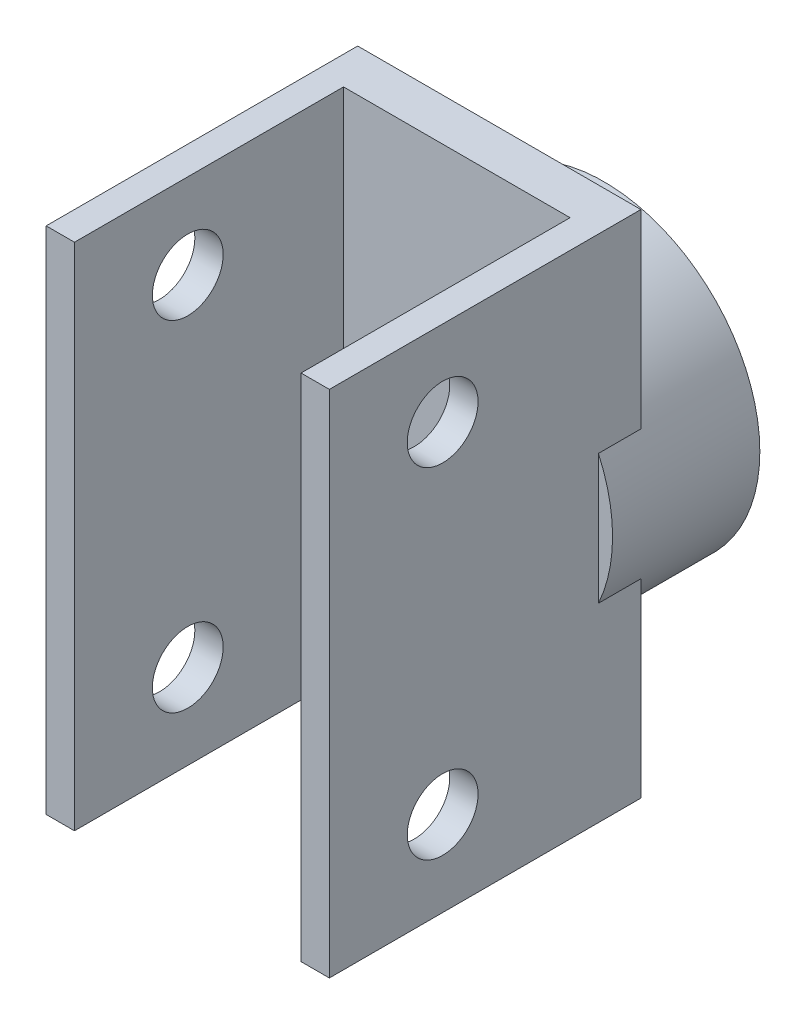
SolidWorks part; units mm, degrees
ref_plane "Front Plane" through (0, 0, 0) normal (0, 0, 1) x (1, 0, 0)
ref_plane "Top Plane" through (0, 0, 0) normal (0, 1, 0) x (1, 0, 0)
ref_plane "Right Plane" through (0, 0, 0) normal (1, 0, 0) x (0, 0, -1)
sketch "Sketch1" plane through (0, 0, 0) normal (0, 0, 1) x (1, 0, 0)
  circle A14 centre (30.5, 45) radius 11
  arc A28 (39.3036, 49.7431) -> (38.5512, 50.9312) centre (30.5, 45) ccw
  arc A29 (33.7877, 49.8991) -> (33.4512, 50.1088) centre (30.5, 45) ccw
  arc A30 (32.2807, 54.8402) -> (30.8827, 54.9927) centre (30.5, 45) ccw
  arc A31 (28.7196, 50.625) -> (28.3458, 50.4927) centre (30.5, 45) ccw
  arc A32 (23.9169, 52.5274) -> (22.926, 51.5295) centre (30.5, 45) ccw
  arc A33 (24.9922, 47.1151) -> (24.8625, 46.7404) centre (30.5, 45) ccw
  arc A34 (20.5103, 44.5464) -> (20.6727, 43.1495) centre (30.5, 45) ccw
  arc A35 (25.4123, 42.0126) -> (25.6244, 41.6776) centre (30.5, 45) ccw
  arc A36 (24.6262, 36.9069) -> (25.8196, 36.1629) centre (30.5, 45) ccw
  arc A37 (29.6635, 39.1596) -> (30.0577, 39.1166) centre (30.5, 45) ccw
  arc A38 (33.1652, 35.3617) -> (34.4909, 35.8309) centre (30.5, 45) ccw
  arc A39 (34.5447, 40.7046) -> (34.824, 40.9859) centre (30.5, 45) ccw
  arc A40 (39.6972, 41.0743) -> (40.157, 42.4034) centre (30.5, 45) ccw
  arc A41 (36.3801, 45.4841) -> (36.3343, 45.8779) centre (30.5, 45) ccw
  arc A42 (39.3036, 49.7431) -> (38.5512, 50.9312) centre (30.5, 45) ccw
  arc A43 (33.7877, 49.8991) -> (33.4512, 50.1088) centre (30.5, 45) ccw
  arc A44 (32.2807, 54.8402) -> (30.8827, 54.9927) centre (30.5, 45) ccw
  arc A45 (28.7196, 50.625) -> (28.3458, 50.4927) centre (30.5, 45) ccw
  arc A46 (23.9169, 52.5274) -> (22.926, 51.5295) centre (30.5, 45) ccw
  arc A47 (24.9922, 47.1151) -> (24.8625, 46.7404) centre (30.5, 45) ccw
  arc A48 (20.5103, 44.5464) -> (20.6727, 43.1495) centre (30.5, 45) ccw
  arc A49 (25.4123, 42.0126) -> (25.6244, 41.6776) centre (30.5, 45) ccw
  arc A50 (24.6262, 36.9069) -> (25.8196, 36.1629) centre (30.5, 45) ccw
  arc A51 (29.6635, 39.1596) -> (30.0577, 39.1166) centre (30.5, 45) ccw
  arc A52 (33.1652, 35.3617) -> (34.4909, 35.8309) centre (30.5, 45) ccw
  arc A53 (34.5447, 40.7046) -> (34.824, 40.9859) centre (30.5, 45) ccw
  arc A54 (39.6972, 41.0743) -> (40.157, 42.4034) centre (30.5, 45) ccw
  arc A55 (36.3801, 45.4841) -> (36.3343, 45.8779) centre (30.5, 45) ccw
  spline S56 degree 3 poles (2006.2188, -3435.1685) (9.1333, 75.8311) (32.642, 44.3935) (37.1296, 46.3932) (37.2493, 46.4533) (37.3624, 46.5251) (37.582, 46.6798) (37.7189, 46.7977) (38.0988, 47.1727) (38.3178, 47.4575) (38.6963, 48.0651) (38.8553, 48.388) (39.0522, 48.8865) (39.1109, 49.0549) (43.146, 62.2268) (-1.8134, 91.7497) (3841.6032, -1191.3469) knots -3.364237 -3.364237 -3.364237 -3.364237 0.03125 0.03125 0.0625 0.125 0.125 0.25 0.25 0.5 0.5 0.75 0.75 0.875 0.875 10.398258 10.398258 10.398258 10.398258 only from (36.9626, 46.326) to (39.3036, 49.7431)
  spline S57 degree 3 poles (585.9272, 4013.0233) (58.3917, -4.1811) (51.4875, 49.0687) (37.8457, 51.0512) (37.6679, 51.0702) (37.1318, 51.1052) (36.7735, 51.0991) (36.0703, 51.0179) (35.7216, 50.9435) (35.2137, 50.7589) (35.0499, 50.6862) (34.8158, 50.5541) (34.7396, 50.5061) (34.6297, 50.4261) (34.5941, 50.3983) (30.8444, 47.1778) (52.1368, 14.8144) (-2579.7529, 3077.4569) knots -9.38856 -9.38856 -9.38856 -9.38856 0.125 0.125 0.25 0.25 0.5 0.5 0.75 0.75 0.875 0.875 0.9375 0.9375 0.96875 0.96875 4.357942 4.357942 4.357942 4.357942 only from (38.5512, 50.9312) to (34.4614, 50.2756)
  spline S58 degree 3 poles (3138.0028, -2472.9908) (-0.1563, 93.9434) (38.2215, 54.6867) (34.2913, 50.0505) (34.2405, 49.9999) (34.1269, 49.9151) (34.0631, 49.88) (29.9182, 48.9815) (6.9004, 135.9751) (3962.2456, 796.0065) knots -21.062428 -21.062428 -21.062428 -21.062428 0.25 0.25 0.5 0.5 0.75 0.75 15.368509 15.368509 15.368509 15.368509 only from (34.4614, 50.2756) to (33.7877, 49.8991)
  spline S59 degree 3 poles (-992.8598, 3914.9682) (120.92, 61.8005) (34.3153, 46.2894) (33.3129, 50.3476) (33.3163, 50.4205) (33.3424, 50.5597) (33.3654, 50.6276) (35.7978, 56.1981) (87.9332, 38.9864) (-3597.2042, 1728.9954) knots -14.205074 -14.205074 -14.205074 -14.205074 0.25 0.25 0.5 0.5 0.75 0.75 22.058789 22.058789 22.058789 22.058789 only from (33.4512, 50.1088) to (33.4927, 50.8794)
  spline S60 degree 3 poles (3983.2458, -580.1704) (-6.9266, 47.5177) (32.3097, 46.2966) (33.5442, 51.0519) (33.5718, 51.183) (33.5863, 51.3161) (33.6022, 51.5843) (33.5955, 51.7648) (33.5391, 52.2956) (33.4529, 52.6444) (33.214, 53.3191) (33.0606, 53.6448) (32.7936, 54.1095) (32.6985, 54.2605) (24.9163, 65.6278) (-26.1974, 48.8843) (3373.2989, 2253.7908) knots -3.364237 -3.364237 -3.364237 -3.364237 0.03125 0.03125 0.0625 0.125 0.125 0.25 0.25 0.5 0.5 0.75 0.75 0.875 0.875 10.398258 10.398258 10.398258 10.398258 only from (33.4927, 50.8794) to (32.2807, 54.8402)
  spline S61 degree 3 poles (-2725.5224, 2953.2725) (86.3416, 36.1427) (40.4044, 63.9455) (30.3489, 54.516) (30.2233, 54.3888) (29.8616, 53.9915) (29.643, 53.7076) (29.268, 53.1072) (29.1088, 52.7881) (28.9365, 52.2759) (28.8912, 52.1026) (28.8485, 51.8372) (28.8385, 51.7476) (28.8325, 51.6119) (28.8321, 51.5667) (29.012, 46.6271) (67.5904, 43.0959) (-3967.8364, -105.072) knots -9.38856 -9.38856 -9.38856 -9.38856 0.125 0.125 0.25 0.25 0.5 0.5 0.75 0.75 0.875 0.875 0.9375 0.9375 0.96875 0.96875 4.357942 4.357942 4.357942 4.357942 only from (30.8827, 54.9927) to (28.8453, 51.3864)
  spline S62 degree 3 poles (3936.6408, 904.6019) (-26.8794, 51.5476) (27.7409, 57.0765) (28.9152, 51.1131) (28.9231, 51.0418) (28.9185, 50.9001) (28.9062, 50.8284) (27.0244, 47.0275) (-55.3413, 83.2711) (1894.7427, 3587.2074) knots -21.062428 -21.062428 -21.062428 -21.062428 0.25 0.25 0.5 0.5 0.75 0.75 15.368509 15.368509 15.368509 15.368509 only from (28.8453, 51.3864) to (28.7196, 50.625)
  spline S63 degree 3 poles (-3633.2174, 1657.7908) (73.7408, 126.1681) (31.8707, 48.7868) (28.0729, 50.5334) (28.0181, 50.5815) (27.9255, 50.6886) (27.8867, 50.7491) (25.0481, 56.1239) (71.0106, 86.1536) (-3547.9372, -1741.2994) knots -14.205074 -14.205074 -14.205074 -14.205074 0.25 0.25 0.5 0.5 0.75 0.75 22.058789 22.058789 22.058789 22.058789 only from (28.3458, 50.4927) to (27.7692, 51.0055)
  spline S64 degree 3 poles (2983.7746, 2745.5937) (5.1964, 17.3085) (30.6146, 47.2233) (27.6665, 51.1533) (27.5812, 51.2567) (27.4861, 51.3509) (27.2864, 51.5307) (27.1411, 51.6379) (26.6909, 51.9248) (26.3645, 52.0749) (25.6879, 52.3088) (25.3377, 52.3919) (24.8079, 52.4729) (24.6306, 52.4927) (10.8911, 53.4957) (-7.8871, 3.094) (387.7989, 4035.664) knots -3.364237 -3.364237 -3.364237 -3.364237 0.03125 0.03125 0.0625 0.125 0.125 0.25 0.25 0.5 0.5 0.75 0.75 0.875 0.875 10.398258 10.398258 10.398258 10.398258 only from (27.7692, 51.0055) to (23.9169, 52.5274)
  spline S65 degree 3 poles (-3961.6309, -296.4668) (72.2416, 83.1363) (21.8631, 64.5559) (22.9659, 50.815) (22.987, 50.6375) (23.0721, 50.107) (23.1578, 49.759) (23.3934, 49.0915) (23.5436, 48.7681) (23.8366, 48.314) (23.9439, 48.1706) (24.1248, 47.9717) (24.1886, 47.9081) (24.291, 47.8188) (24.3261, 47.7902) (28.3002, 44.8511) (55.1141, 72.8112) (-2345.091, -3174.5936) knots -9.38856 -9.38856 -9.38856 -9.38856 0.125 0.125 0.25 0.25 0.5 0.5 0.75 0.75 0.875 0.875 0.9375 0.9375 0.96875 0.96875 4.357942 4.357942 4.357942 4.357942 only from (22.926, 51.5295) to (24.4752, 47.6881)
  spline S66 degree 3 poles (1793.8751, 3634.8969) (-10.3946, 4.2214) (19.338, 50.3724) (24.7325, 47.5724) (24.7931, 47.5341) (24.9011, 47.4422) (24.9495, 47.3879) (26.7478, 43.5468) (-52.9427, 1.7483) (-1576.5729, 3711.0538) knots -21.062428 -21.062428 -21.062428 -21.062428 0.25 0.25 0.5 0.5 0.75 0.75 15.368509 15.368509 15.368509 15.368509 only from (24.4752, 47.6881) to (24.9922, 47.1151)
  spline S67 degree 3 poles (-3514.7211, -1813.851) (-5.9996, 129.4145) (28.394, 48.4327) (24.6606, 46.5524) (24.5888, 46.5395) (24.4472, 46.5339) (24.3758, 46.5413) (18.4037, 47.6732) (23.5828, 102.3313) (-804.034, -3866.4743) knots -14.205074 -14.205074 -14.205074 -14.205074 0.25 0.25 0.5 0.5 0.75 0.75 22.058789 22.058789 22.058789 22.058789 only from (24.8625, 46.7404) to (24.102, 46.6093)
  spline S68 degree 3 poles (-239.5726, 4037.7557) (36.3736, 7.9515) (28.8332, 46.4758) (23.9224, 46.6212) (23.7885, 46.619) (23.6555, 46.6034) (23.3905, 46.5593) (23.216, 46.5125) (22.711, 46.3394) (22.3901, 46.1778) (21.7855, 45.7947) (21.5021, 45.5727) (21.1085, 45.2091) (20.9825, 45.0827) (11.6319, 34.9661) (39.3295, -11.1402) (-2866.7545, 2812.4858) knots -3.364237 -3.364237 -3.364237 -3.364237 0.03125 0.03125 0.0625 0.125 0.125 0.25 0.25 0.5 0.5 0.75 0.75 0.875 0.875 10.398258 10.398258 10.398258 10.398258 only from (24.102, 46.6093) to (20.5103, 44.5464)
  spline S69 degree 3 poles (-2191.5834, -3289.0747) (26.7093, 101.4124) (9.8256, 50.4403) (21.2562, 42.7352) (21.4082, 42.641) (21.876, 42.3768) (22.2015, 42.2268) (22.8702, 41.9949) (23.2167, 41.9106) (23.7544, 41.8566) (23.9335, 41.8511) (24.2018, 41.8685) (24.2913, 41.8787) (24.425, 41.9031) (24.4691, 41.9127) (29.2448, 43.1873) (24.1029, 81.5841) (1066.5229, -3819.6956) knots -9.38856 -9.38856 -9.38856 -9.38856 0.125 0.125 0.25 0.25 0.5 0.5 0.75 0.75 0.875 0.875 0.9375 0.9375 0.96875 0.96875 4.357942 4.357942 4.357942 4.357942 only from (20.6727, 43.1495) to (24.642, 41.9656)
  spline S70 degree 3 poles (-1676.748, 3661.9263) (36.8847, -12.3977) (19.3403, 39.6228) (24.8928, 42.0946) (24.9605, 42.1182) (25.0997, 42.1453) (25.1724, 42.1493) (29.2967, 41.1604) (12.2899, -47.2052) (-3837.7299, 1074.287) knots -21.062428 -21.062428 -21.062428 -21.062428 0.25 0.25 0.5 0.5 0.75 0.75 15.368509 15.368509 15.368509 15.368509 only from (24.642, 41.9656) to (25.4123, 42.0126)
  spline S71 degree 3 poles (-726.601, -3885.7401) (-58.2551, 69.0951) (26.5031, 45.4937) (25.6455, 41.4025) (25.6108, 41.3383) (25.5269, 41.2242) (25.4766, 41.1729) (20.8681, 37.2095) (-18.6363, 75.3374) (2568.2903, -3046.2293) knots -14.205074 -14.205074 -14.205074 -14.205074 0.25 0.25 0.5 0.5 0.75 0.75 22.058789 22.058789 22.058789 22.058789 only from (25.6244, 41.6776) to (25.2527, 41.0013)
  spline S72 degree 3 poles (-3259.5497, 2323.2912) (63.1278, 26.4928) (28.307, 44.617) (25.1315, 40.8683) (25.0497, 40.7622) (24.9789, 40.6485) (24.8482, 40.4137) (24.7759, 40.2482) (24.5964, 39.7455) (24.5227, 39.3938) (24.4453, 38.6822) (24.4421, 38.3223) (24.481, 37.7878) (24.5012, 37.6105) (26.5807, 23.9923) (79.8973, 16.9003) (-3939.6162, -494.6656) knots -3.364237 -3.364237 -3.364237 -3.364237 0.03125 0.03125 0.0625 0.125 0.125 0.25 0.25 0.5 0.5 0.75 0.75 0.875 0.875 10.398258 10.398258 10.398258 10.398258 only from (25.2527, 41.0013) to (24.6262, 36.9069)
  spline S73 degree 3 poles (1251.7382, -3771.0563) (-15.9685, 77.2089) (13.3563, 32.2281) (26.5073, 36.3609) (26.6757, 36.4209) (27.1739, 36.622) (27.4941, 36.7829) (28.0924, 37.1612) (28.3743, 37.3795) (28.7518, 37.7662) (28.8678, 37.9028) (29.0214, 38.1234) (29.0693, 38.1997) (29.1335, 38.3194) (29.1536, 38.36) (31.1346, 42.8884) (-2.0911, 62.8084) (3697.9904, -1554.603) knots -9.38856 -9.38856 -9.38856 -9.38856 0.125 0.125 0.25 0.25 0.5 0.5 0.75 0.75 0.875 0.875 0.9375 0.9375 0.96875 0.96875 4.357942 4.357942 4.357942 4.357942 only from (25.8196, 36.1629) to (29.2199, 38.5281)
  spline S74 degree 3 poles (-3861.7785, 965.3364) (79.3561, 14.2048) (27.7461, 32.9223) (29.2755, 38.8046) (29.2993, 38.8723) (29.3649, 38.998) (29.4071, 39.0573) (32.7517, 41.6652) (91.2351, -26.7262) (-3186.0308, -2337.554) knots -21.062428 -21.062428 -21.062428 -21.062428 0.25 0.25 0.5 0.5 0.75 0.75 15.368509 15.368509 15.368509 15.368509 only from (29.2199, 38.5281) to (29.6635, 39.1596)
  spline S75 degree 3 poles (2631.6316, -2997.7017) (-43.6762, -9.3685) (27.622, 42.1829) (30.2859, 38.9615) (30.3145, 38.8944) (30.3514, 38.7577) (30.3601, 38.6864) (30.5855, 32.6122) (-23.8547, 25.4988) (4029.6068, 101.7745) knots -14.205074 -14.205074 -14.205074 -14.205074 0.25 0.25 0.5 0.5 0.75 0.75 22.058789 22.058789 22.058789 22.058789 only from (30.0577, 39.1166) to (30.3547, 38.4043)
  spline S76 degree 3 poles (-3802.0522, -1106.773) (65.3126, 58.9704) (29.4321, 43.0466) (30.3831, 38.2266) (30.415, 38.0965) (30.4598, 37.9703) (30.5618, 37.7217) (30.6462, 37.562) (30.9273, 37.1083) (31.1563, 36.8314) (31.6644, 36.3272) (31.9438, 36.1003) (32.386, 35.7974) (32.5372, 35.7027) (44.4808, 28.8377) (83.268, 66.1005) (-2022.8994, -3395.4378) knots -3.364237 -3.364237 -3.364237 -3.364237 0.03125 0.03125 0.0625 0.125 0.125 0.25 0.25 0.5 0.5 0.75 0.75 0.875 0.875 10.398258 10.398258 10.398258 10.398258 only from (30.3547, 38.4043) to (33.1652, 35.3617)
  spline S77 degree 3 poles (3775.4425, -1379.4697) (-23.6545, 28.7514) (29.7966, 23.6333) (34.7649, 36.4919) (34.823, 36.661) (34.9764, 37.1759) (35.0502, 37.5266) (35.1275, 38.2302) (35.1326, 38.5868) (35.0656, 39.123) (35.0312, 39.2988) (34.9544, 39.5565) (34.9247, 39.6415) (34.8711, 39.7664) (34.8519, 39.8073) (32.5466, 44.1796) (-3.7434, 30.6226) (3567.7628, 1915.0233) knots -9.38856 -9.38856 -9.38856 -9.38856 0.125 0.125 0.25 0.25 0.5 0.5 0.75 0.75 0.875 0.875 0.9375 0.9375 0.96875 0.96875 4.357942 4.357942 4.357942 4.357942 only from (34.4909, 35.8309) to (34.7618, 39.964)
  spline S78 degree 3 poles (-3115.844, -2424.2855) (85.0379, 63.9968) (38.2257, 35.3166) (34.5802, 40.1799) (34.5422, 40.2407) (34.4848, 40.3703) (34.4648, 40.4403) (34.5111, 44.6813) (124.4455, 47.764) (-112.2185, -3955.2832) knots -21.062428 -21.062428 -21.062428 -21.062428 0.25 0.25 0.5 0.5 0.75 0.75 15.368509 15.368509 15.368509 15.368509 only from (34.7618, 39.964) to (34.5447, 40.7046)
  spline S79 degree 3 poles (4031.159, 181.5531) (26.7589, -46.8915) (30.9081, 40.9934) (35.0876, 41.0677) (35.1579, 41.0482) (35.2878, 40.9918) (35.3489, 40.9541) (40.2385, 37.3432) (11.8571, -9.655) (2479.5142, 3207.0259) knots -14.205074 -14.205074 -14.205074 -14.205074 0.25 0.25 0.5 0.5 0.75 0.75 22.058789 22.058789 22.058789 22.058789 only from (34.824, 40.9859) to (35.5661, 40.7741)
  spline S80 degree 3 poles (-1458.5648, -3669.5287) (41.2828, 80.928) (31.3614, 42.9472) (35.7228, 40.6855) (35.8444, 40.6293) (35.971, 40.5857) (36.2289, 40.5104) (36.4064, 40.4768) (36.9365, 40.4137) (37.2957, 40.4201) (38.0067, 40.5029) (38.3583, 40.58) (38.8707, 40.7368) (39.0391, 40.796) (51.8531, 45.8536) (46.9033, 99.4116) (1440.069, -3705.4902) knots -3.364237 -3.364237 -3.364237 -3.364237 0.03125 0.03125 0.0625 0.125 0.125 0.25 0.25 0.5 0.5 0.75 0.75 0.875 0.875 10.398258 10.398258 10.398258 10.398258 only from (35.5661, 40.7741) to (39.6972, 41.0743)
  spline S81 degree 3 poles (3479.1288, 2084.7716) (9.4389, -7.4706) (46.7666, 31.1281) (39.811, 43.0298) (39.715, 43.1806) (39.4081, 43.6216) (39.18, 43.8979) (38.678, 44.3971) (38.4025, 44.6233) (37.9414, 44.9053) (37.7825, 44.988) (37.5332, 45.0887) (37.4482, 45.1184) (37.3171, 45.1544) (37.2732, 45.1649) (32.4174, 46.0886) (20.3903, 9.2633) (773.9042, 3976.4839) knots -9.38856 -9.38856 -9.38856 -9.38856 0.125 0.125 0.25 0.25 0.5 0.5 0.75 0.75 0.875 0.875 0.9375 0.9375 0.96875 0.96875 4.357942 4.357942 4.357942 4.357942 only from (40.157, 42.4034) to (37.0945, 45.1922)
  spline S82 degree 3 poles (-0.6482, -3954.4851) (49.6516, 99.4838) (42.8876, 45.0027) (36.8125, 45.1848) (36.7412, 45.1929) (36.6041, 45.2289) (36.5369, 45.2569) (33.2501, 47.9373) (86.9131, 120.1729) (3069.0638, -2560.7175) knots -21.062428 -21.062428 -21.062428 -21.062428 0.25 0.25 0.5 0.5 0.75 0.75 15.368509 15.368509 15.368509 15.368509 only from (37.0945, 45.1922) to (36.3801, 45.4841)
  spline S83 degree 3 poles (2418.1086, 3257.9806) (100.0111, -15.2183) (33.8869, 42.821) (36.4347, 46.1349) (36.4938, 46.1777) (36.6189, 46.2442) (36.6864, 46.2685) (42.5582, 47.8399) (61.6073, -3.6525) (-914.736, 3931.2073) knots -14.205074 -14.205074 -14.205074 -14.205074 0.25 0.25 0.5 0.5 0.75 0.75 22.058789 22.058789 22.058789 22.058789 only from (36.3343, 45.8779) to (36.9626, 46.326)
  spline S84 degree 3 poles (36.9626, 46.326) (37.0052, 46.3414) (37.0477, 46.3568) (37.1296, 46.3932) (37.2493, 46.4533) (37.3624, 46.5251) (37.582, 46.6798) (37.7189, 46.7977) (38.0988, 47.1727) (38.3178, 47.4575) (38.6963, 48.0651) (38.8553, 48.388) (39.0522, 48.8865) (39.1109, 49.0549) (39.2154, 49.3962) (39.2593, 49.5697) (39.3036, 49.7431) knots 0 0 0 0 0.03125 0.03125 0.0625 0.125 0.125 0.25 0.25 0.5 0.5 0.75 0.75 0.875 0.875 1 1 1 1
  spline S85 degree 3 poles (38.5512, 50.9312) (38.3753, 50.9652) (38.1995, 50.9998) (37.8457, 51.0512) (37.6679, 51.0702) (37.1318, 51.1052) (36.7735, 51.0991) (36.0703, 51.0179) (35.7216, 50.9435) (35.2137, 50.7589) (35.0499, 50.6862) (34.8158, 50.5541) (34.7396, 50.5061) (34.6297, 50.4261) (34.5941, 50.3983) (34.5256, 50.3394) (34.4935, 50.3075) (34.4614, 50.2756) knots 0 0 0 0 0.125 0.125 0.25 0.25 0.5 0.5 0.75 0.75 0.875 0.875 0.9375 0.9375 0.96875 0.96875 1 1 1 1
  spline S86 degree 3 poles (34.4614, 50.2756) (34.4222, 50.2165) (34.3825, 50.158) (34.2913, 50.0505) (34.2405, 49.9999) (34.1269, 49.9151) (34.0631, 49.88) (33.9237, 49.8498) (33.8485, 49.8604) (33.7877, 49.8991) knots 0 0 0 0 0.25 0.25 0.5 0.5 0.75 0.75 1 1 1 1
  spline S87 degree 3 poles (33.4512, 50.1088) (33.3896, 50.1464) (33.347, 50.2096) (33.3129, 50.3476) (33.3163, 50.4205) (33.3424, 50.5597) (33.3654, 50.6276) (33.4218, 50.7568) (33.4569, 50.8183) (33.4927, 50.8794) knots 0 0 0 0 0.25 0.25 0.5 0.5 0.75 0.75 1 1 1 1
  spline S88 degree 3 poles (33.4927, 50.8794) (33.5072, 50.9223) (33.5217, 50.9652) (33.5442, 51.0519) (33.5718, 51.183) (33.5863, 51.3161) (33.6022, 51.5843) (33.5955, 51.7648) (33.5391, 52.2956) (33.4529, 52.6444) (33.214, 53.3191) (33.0606, 53.6448) (32.7936, 54.1095) (32.6985, 54.2605) (32.4969, 54.555) (32.3886, 54.6975) (32.2807, 54.8402) knots 0 0 0 0 0.03125 0.03125 0.0625 0.125 0.125 0.25 0.25 0.5 0.5 0.75 0.75 0.875 0.875 1 1 1 1
  spline S89 degree 3 poles (30.8827, 54.9927) (30.7464, 54.8764) (30.6098, 54.7606) (30.3489, 54.516) (30.2233, 54.3888) (29.8616, 53.9915) (29.643, 53.7076) (29.268, 53.1072) (29.1088, 52.7881) (28.9365, 52.2759) (28.8912, 52.1026) (28.8485, 51.8372) (28.8385, 51.7476) (28.8325, 51.6119) (28.8321, 51.5667) (28.8354, 51.4764) (28.8403, 51.4314) (28.8453, 51.3864) knots 0 0 0 0 0.125 0.125 0.25 0.25 0.5 0.5 0.75 0.75 0.875 0.875 0.9375 0.9375 0.96875 0.96875 1 1 1 1
  spline S90 degree 3 poles (28.8453, 51.3864) (28.867, 51.319) (28.888, 51.2514) (28.9152, 51.1131) (28.9231, 51.0418) (28.9185, 50.9001) (28.9062, 50.8284) (28.8429, 50.7005) (28.7878, 50.6483) (28.7196, 50.625) knots 0 0 0 0 0.25 0.25 0.5 0.5 0.75 0.75 1 1 1 1
  spline S91 degree 3 poles (28.3458, 50.4927) (28.278, 50.4679) (28.202, 50.474) (28.0729, 50.5334) (28.0181, 50.5815) (27.9255, 50.6886) (27.8867, 50.7491) (27.8209, 50.8737) (27.7947, 50.9395) (27.7692, 51.0055) knots 0 0 0 0 0.25 0.25 0.5 0.5 0.75 0.75 1 1 1 1
  spline S92 degree 3 poles (27.7692, 51.0055) (27.7447, 51.0436) (27.7202, 51.0817) (27.6665, 51.1533) (27.5812, 51.2567) (27.4861, 51.3509) (27.2864, 51.5307) (27.1411, 51.6379) (26.6909, 51.9248) (26.3645, 52.0749) (25.6879, 52.3088) (25.3377, 52.3919) (24.8079, 52.4729) (24.6306, 52.4927) (24.2746, 52.5187) (24.0957, 52.5228) (23.9169, 52.5274) knots 0 0 0 0 0.03125 0.03125 0.0625 0.125 0.125 0.25 0.25 0.5 0.5 0.75 0.75 0.875 0.875 1 1 1 1
  spline S93 degree 3 poles (22.926, 51.5295) (22.9319, 51.3505) (22.9373, 51.1714) (22.9659, 50.815) (22.987, 50.6375) (23.0721, 50.107) (23.1578, 49.759) (23.3934, 49.0915) (23.5436, 48.7681) (23.8366, 48.314) (23.9439, 48.1706) (24.1248, 47.9717) (24.1886, 47.9081) (24.291, 47.8188) (24.3261, 47.7902) (24.3987, 47.7365) (24.4369, 47.7123) (24.4752, 47.6881) knots 0 0 0 0 0.125 0.125 0.25 0.25 0.5 0.5 0.75 0.75 0.875 0.875 0.9375 0.9375 0.96875 0.96875 1 1 1 1
  spline S94 degree 3 poles (24.4752, 47.6881) (24.5415, 47.6631) (24.6074, 47.6374) (24.7325, 47.5724) (24.7931, 47.5341) (24.9011, 47.4422) (24.9495, 47.3879) (25.01, 47.2587) (25.0164, 47.183) (24.9922, 47.1151) knots 0 0 0 0 0.25 0.25 0.5 0.5 0.75 0.75 1 1 1 1
  spline S95 degree 3 poles (24.8625, 46.7404) (24.8396, 46.672) (24.7875, 46.6164) (24.6606, 46.5524) (24.5888, 46.5395) (24.4472, 46.5339) (24.3758, 46.5413) (24.2373, 46.5676) (24.1696, 46.5881) (24.102, 46.6093) knots 0 0 0 0 0.25 0.25 0.5 0.5 0.75 0.75 1 1 1 1
  spline S96 degree 3 poles (24.102, 46.6093) (24.057, 46.614) (24.012, 46.6185) (23.9224, 46.6212) (23.7885, 46.619) (23.6555, 46.6034) (23.3905, 46.5593) (23.216, 46.5125) (22.711, 46.3394) (22.3901, 46.1778) (21.7855, 45.7947) (21.5021, 45.5727) (21.1085, 45.2091) (20.9825, 45.0827) (20.7402, 44.8206) (20.6254, 44.6833) (20.5103, 44.5464) knots 0 0 0 0 0.03125 0.03125 0.0625 0.125 0.125 0.25 0.25 0.5 0.5 0.75 0.75 0.875 0.875 1 1 1 1
  spline S97 degree 3 poles (20.6727, 43.1495) (20.8164, 43.0425) (20.9597, 42.9351) (21.2562, 42.7352) (21.4082, 42.641) (21.876, 42.3768) (22.2015, 42.2268) (22.8702, 41.9949) (23.2167, 41.9106) (23.7544, 41.8566) (23.9335, 41.8511) (24.2018, 41.8685) (24.2913, 41.8787) (24.425, 41.9031) (24.4691, 41.9127) (24.5564, 41.936) (24.5992, 41.9508) (24.642, 41.9656) knots 0 0 0 0 0.125 0.125 0.25 0.25 0.5 0.5 0.75 0.75 0.875 0.875 0.9375 0.9375 0.96875 0.96875 1 1 1 1
  spline S98 degree 3 poles (24.642, 41.9656) (24.7028, 42.0018) (24.764, 42.0373) (24.8928, 42.0946) (24.9605, 42.1182) (25.0997, 42.1453) (25.1724, 42.1493) (25.3111, 42.116) (25.3743, 42.0738) (25.4123, 42.0126) knots 0 0 0 0 0.25 0.25 0.5 0.5 0.75 0.75 1 1 1 1
  spline S99 degree 3 poles (25.6244, 41.6776) (25.6636, 41.617) (25.6746, 41.5416) (25.6455, 41.4025) (25.6108, 41.3383) (25.5269, 41.2242) (25.4766, 41.1729) (25.3697, 41.081) (25.3115, 41.0408) (25.2527, 41.0013) knots 0 0 0 0 0.25 0.25 0.5 0.5 0.75 0.75 1 1 1 1
  spline S100 degree 3 poles (25.2527, 41.0013) (25.221, 40.969) (25.1894, 40.9366) (25.1315, 40.8683) (25.0497, 40.7622) (24.9789, 40.6485) (24.8482, 40.4137) (24.7759, 40.2482) (24.5964, 39.7455) (24.5227, 39.3938) (24.4453, 38.6822) (24.4421, 38.3223) (24.481, 37.7878) (24.5012, 37.6105) (24.5551, 37.2576) (24.5909, 37.0823) (24.6262, 36.9069) knots 0 0 0 0 0.03125 0.03125 0.0625 0.125 0.125 0.25 0.25 0.5 0.5 0.75 0.75 0.875 0.875 1 1 1 1
  spline S101 degree 3 poles (25.8196, 36.1629) (25.9928, 36.2085) (26.1662, 36.2537) (26.5073, 36.3609) (26.6757, 36.4209) (27.1739, 36.622) (27.4941, 36.7829) (28.0924, 37.1612) (28.3743, 37.3795) (28.7518, 37.7662) (28.8678, 37.9028) (29.0214, 38.1234) (29.0693, 38.1997) (29.1335, 38.3194) (29.1536, 38.36) (29.1898, 38.4427) (29.2049, 38.4854) (29.2199, 38.5281) knots 0 0 0 0 0.125 0.125 0.25 0.25 0.5 0.5 0.75 0.75 0.875 0.875 0.9375 0.9375 0.96875 0.96875 1 1 1 1
  spline S102 degree 3 poles (29.2199, 38.5281) (29.2296, 38.5983) (29.24, 38.6682) (29.2755, 38.8046) (29.2993, 38.8723) (29.3649, 38.998) (29.4071, 39.0573) (29.5196, 39.145) (29.592, 39.1681) (29.6635, 39.1596) knots 0 0 0 0 0.25 0.25 0.5 0.5 0.75 0.75 1 1 1 1
  spline S103 degree 3 poles (30.0577, 39.1166) (30.1295, 39.1095) (30.1953, 39.0711) (30.2859, 38.9615) (30.3145, 38.8944) (30.3514, 38.7577) (30.3601, 38.6864) (30.3653, 38.5455) (30.3604, 38.4749) (30.3547, 38.4043) knots 0 0 0 0 0.25 0.25 0.5 0.5 0.75 0.75 1 1 1 1
  spline S104 degree 3 poles (30.3547, 38.4043) (30.3602, 38.3594) (30.3657, 38.3145) (30.3831, 38.2266) (30.415, 38.0965) (30.4598, 37.9703) (30.5618, 37.7217) (30.6462, 37.562) (30.9273, 37.1083) (31.1563, 36.8314) (31.6644, 36.3272) (31.9438, 36.1003) (32.386, 35.7974) (32.5372, 35.7027) (32.8467, 35.5248) (33.006, 35.4435) (33.1652, 35.3617) knots 0 0 0 0 0.03125 0.03125 0.0625 0.125 0.125 0.25 0.25 0.5 0.5 0.75 0.75 0.875 0.875 1 1 1 1
  spline S105 degree 3 poles (34.4909, 35.8309) (34.5632, 35.9947) (34.6361, 36.1584) (34.7649, 36.4919) (34.823, 36.661) (34.9764, 37.1759) (35.0502, 37.5266) (35.1275, 38.2302) (35.1326, 38.5868) (35.0656, 39.123) (35.0312, 39.2988) (34.9544, 39.5565) (34.9247, 39.6415) (34.8711, 39.7664) (34.8519, 39.8073) (34.8098, 39.8872) (34.7858, 39.9256) (34.7618, 39.964) knots 0 0 0 0 0.125 0.125 0.25 0.25 0.5 0.5 0.75 0.75 0.875 0.875 0.9375 0.9375 0.96875 0.96875 1 1 1 1
  spline S106 degree 3 poles (34.7618, 39.964) (34.713, 40.0153) (34.6648, 40.0671) (34.5802, 40.1799) (34.5422, 40.2407) (34.4848, 40.3703) (34.4648, 40.4403) (34.4663, 40.583) (34.4934, 40.6539) (34.5447, 40.7046) knots 0 0 0 0 0.25 0.25 0.5 0.5 0.75 0.75 1 1 1 1
  spline S107 degree 3 poles (34.824, 40.9859) (34.8744, 41.0376) (34.9454, 41.0652) (35.0876, 41.0677) (35.1579, 41.0482) (35.2878, 40.9918) (35.3489, 40.9541) (35.4623, 40.8704) (35.5145, 40.8225) (35.5661, 40.7741) knots 0 0 0 0 0.25 0.25 0.5 0.5 0.75 0.75 1 1 1 1
  spline S108 degree 3 poles (35.5661, 40.7741) (35.6047, 40.7504) (35.6432, 40.7267) (35.7228, 40.6855) (35.8444, 40.6293) (35.971, 40.5857) (36.2289, 40.5104) (36.4064, 40.4768) (36.9365, 40.4137) (37.2957, 40.4201) (38.0067, 40.5029) (38.3583, 40.58) (38.8707, 40.7368) (39.0391, 40.796) (39.3711, 40.927) (39.5341, 41.0009) (39.6972, 41.0743) knots 0 0 0 0 0.03125 0.03125 0.0625 0.125 0.125 0.25 0.25 0.5 0.5 0.75 0.75 0.875 0.875 1 1 1 1
  spline S109 degree 3 poles (40.157, 42.4034) (40.074, 42.5621) (39.9914, 42.7211) (39.811, 43.0298) (39.715, 43.1806) (39.4081, 43.6216) (39.18, 43.8979) (38.678, 44.3971) (38.4025, 44.6233) (37.9414, 44.9053) (37.7825, 44.988) (37.5332, 45.0887) (37.4482, 45.1184) (37.3171, 45.1544) (37.2732, 45.1649) (37.1844, 45.1817) (37.1395, 45.187) (37.0945, 45.1922) knots 0 0 0 0 0.125 0.125 0.25 0.25 0.5 0.5 0.75 0.75 0.875 0.875 0.9375 0.9375 0.96875 0.96875 1 1 1 1
  spline S110 degree 3 poles (37.0945, 45.1922) (37.0239, 45.1859) (36.9534, 45.1805) (36.8125, 45.1848) (36.7412, 45.1929) (36.6041, 45.2289) (36.5369, 45.2569) (36.4264, 45.347) (36.3877, 45.4124) (36.3801, 45.4841) knots 0 0 0 0 0.25 0.25 0.5 0.5 0.75 0.75 1 1 1 1
  spline S111 degree 3 poles (36.3343, 45.8779) (36.3253, 45.9495) (36.3481, 46.0223) (36.4347, 46.1349) (36.4938, 46.1777) (36.6189, 46.2442) (36.6864, 46.2685) (36.8226, 46.3049) (36.8925, 46.3159) (36.9626, 46.326) knots 0 0 0 0 0.25 0.25 0.5 0.5 0.75 0.75 1 1 1 1
  dimension "D2" = 22
  dimension "D1" = 0.5
extrude "Boss-Extrude1" add sketch "Sketch1" along normal up to surface (7.4 mm away)
sketch "Sketch3" plane through (0, 0, 7.4) normal (0, 0, 1) x (1, 0, 0)
  circle A0 centre (30.5, 45) radius 11 construction
  circle A1 centre (30.5, 45) radius 11
extrude "Boss-Extrude2" add sketch "Sketch3" along normal blind 3
sketch "Sketch4" plane through (0, 0, 10.4) normal (0, 0, 1) x (1, 0, 0)
  line L1 (20.5, 63) -> (40.5, 63)
  line L2 (20.5, 63) -> (20.5, 27)
  line L3 (20.5, 27) -> (40.5, 27)
  line L4 (40.5, 63) -> (40.5, 27)
  line L5 (20.5, 63) -> (40.5, 27) construction
  line L6 (20.5, 27) -> (40.5, 63) construction
  point P0 (30.5, 45)
  dimension "D1" = 20
  dimension "D2" = 36
extrude "Boss-Extrude3" add sketch "Sketch4" against normal blind 3
sketch "Sketch5" plane through (0, 0, 10.4) normal (0, 0, 1) x (1, 0, 0)
  line L0 (20.5, 27) -> (40.5, 27) construction
  line L1 (20.5, 63) -> (22.5, 63)
  line L2 (20.5, 63) -> (20.5, 27)
  line L3 (20.5, 27) -> (22.5, 27)
  line L4 (22.5, 63) -> (22.5, 27)
  line L6 (40.5, 63) -> (38.5, 63)
  line L7 (40.5, 63) -> (40.5, 27)
  line L8 (40.5, 27) -> (38.5, 27)
  line L9 (38.5, 63) -> (38.5, 27)
  dimension "D1" = 2
  dimension "D2" = 2
extrude "Boss-Extrude4" add sketch "Sketch5" along normal blind 19
sketch "Sketch6" plane through (40.5, 0, 0) normal (1, 0, 0) x (0, 0, -1)
  line L0 (-7.4, 27) -> (-29.4, 27) construction
  line L2 (-29.4, 27) -> (-29.4, 63) construction
  line L3 (-7.4, 63) -> (-29.4, 63) construction
  circle A0 centre (-21.4, 33) radius 2.5
  circle A1 centre (-21.4, 57) radius 2.5
  point P4 (-20.8722, 31.7981)
  point P9 (-29.4, 30.1868)
  point P12 (0, 0)
  dimension "D1" = 5
  dimension "D2" = 5
  dimension "D3" = 6
  dimension "D4" = 8
  dimension "D5" = 6
extrude "Cut-Extrude1" cut sketch "Sketch6" against normal through all
